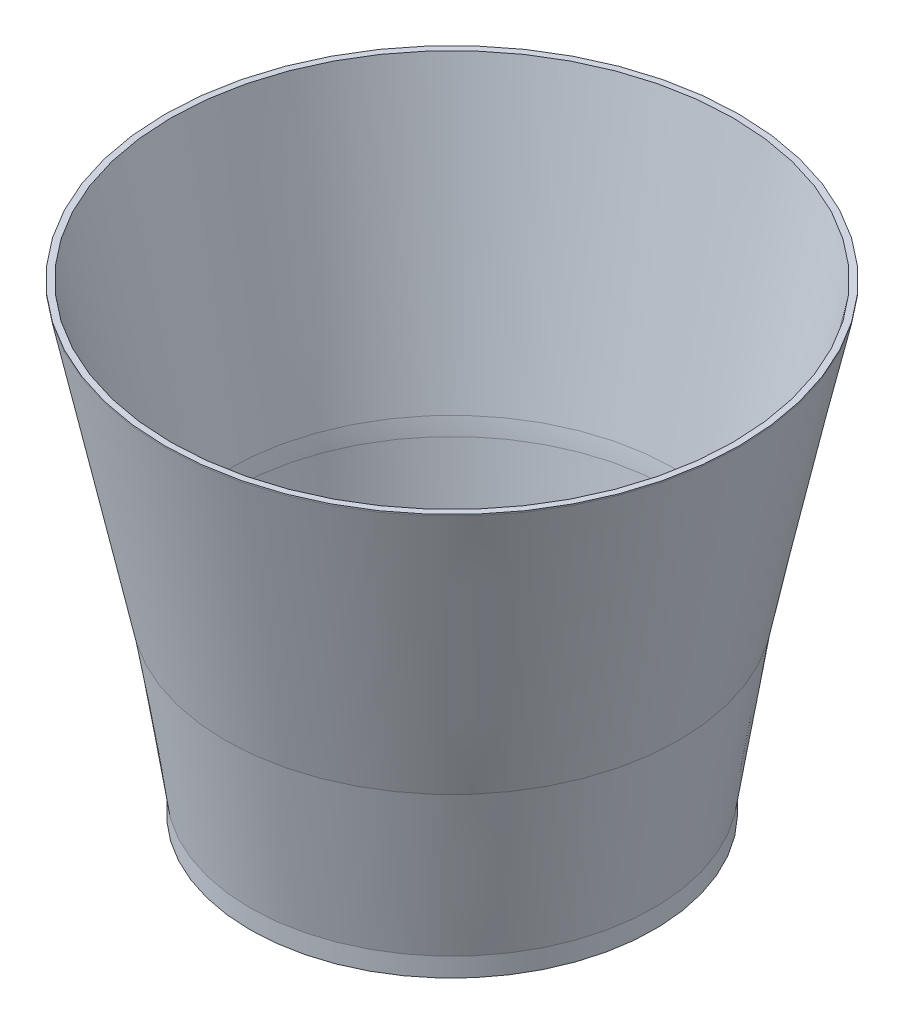
SolidWorks part; units mm, degrees
ref_plane "Front Plane" through (0, 0, 0) normal (0, 0, 1) x (1, 0, 0)
ref_plane "Top Plane" through (0, 0, 0) normal (0, 1, 0) x (1, 0, 0)
ref_plane "Right Plane" through (0, 0, 0) normal (1, 0, 0) x (0, 0, -1)
sketch "Sketch1" plane through (0, 0, 0) normal (0, 1, 0) x (1, 0, 0)
  circle A0 centre (0, 0) radius 32
  circle A1 centre (-1.0593, 9.9437) radius 2
  circle A2 centre (0.5297, -4.9719) radius 2
  circle A4 centre (0, 21.1624) radius 4
  circle A5 centre (16.5454, 13.1945) radius 4
  circle A6 centre (20.6318, -4.7091) radius 4
  circle A7 centre (9.182, -19.0667) radius 4
  circle A8 centre (-9.182, -19.0667) radius 4
  circle A9 centre (-20.6318, -4.7091) radius 4
  circle A10 centre (-16.5454, 13.1945) radius 4
  point P26 (0, 0)
  dimension "D1" = 64
  dimension "D2" = 7
extrude "Boss-Extrude1" add sketch "Sketch1" along normal blind 3
sketch "Sketch3" plane through (0, 0, 0) normal (1, 0, 0) x (0, 0, -1)
  line L0 (-32, 3) -> (-35.9596, 28)
  line L1 (0, 0) -> (0, 36.9962) construction
  line L2 (-31, 3) -> (32, 3) construction
  line L3 (-35.9596, 28) -> (-34.9596, 28)
  line L4 (-34.9596, 28) -> (-30.5248, 0)
  line L5 (-30.5248, 0) -> (-32, 0)
  line L6 (-32, 0) -> (-32, 3)
  line L7 (32, 3) -> (-32, 3) construction
  dimension "D1" = 99
  dimension "D2" = 25
  dimension "D3" = 1
revolve "Revolve2" add sketch "Sketch3" angle 360 about L1
sketch "Sketch5" plane through (0, 0, 0) normal (1, 0, 0) x (0, 0, -1)
  line L0 (-35.9596, 28) -> (-45.5247, 73)
  line L1 (-34.9815, 28.2079) -> (-44.5465, 73.2079)
  line L2 (-32, 3) -> (-44.5945, 82.5186) construction
  line L3 (-35.9596, 28) -> (-34.9596, 28)
  line L4 (-34.9596, 28) -> (-34.9815, 28.2079)
  line L5 (-44.5465, 73.2079) -> (-45.5247, 73.2079)
  line L6 (-45.5247, 73.2079) -> (-45.5247, 73)
  dimension "D1" = 3
  dimension "D2" = 45
  dimension "D3" = 1
revolve "Revolve3" add sketch "Sketch5" angle 360 about L1
fillet "Fillet1" radius 50 1 edges at (0, 28.2079, -34.9815)
